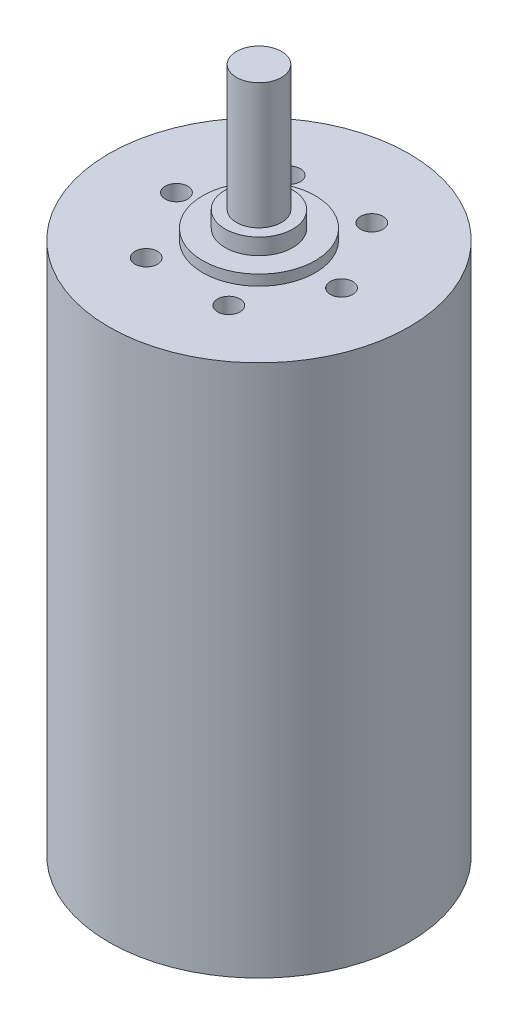
SolidWorks part; units mm, degrees
ref_plane "Front Plane" through (0, 0, 0) normal (0, 0, 1) x (1, 0, 0)
ref_plane "Top Plane" through (0, 0, 0) normal (0, 1, 0) x (1, 0, 0)
ref_plane "Right Plane" through (0, 0, 0) normal (1, 0, 0) x (0, 0, -1)
sketch "Sketch1" plane through (0, 0, 0) normal (0, 1, 0) x (1, 0, 0)
  circle A0 centre (0, 0) radius 20
  dimension "D1" = 40
extrude "Boss-Extrude1" add sketch "Sketch1" along normal blind 71
sketch "Sketch2" plane through (0, 71, 0) normal (0, 1, 0) x (1, 0, 0)
  circle A0 centre (0, 0) radius 7.5
  dimension "D1" = 15
extrude "Boss-Extrude2" add sketch "Sketch2" along normal blind 1.4
sketch "Sketch3" plane through (0, 72.4, 0) normal (0, 1, 0) x (1, 0, 0)
  circle A0 centre (0, 0) radius 4.5
  dimension "D1" = 9
extrude "Boss-Extrude3" add sketch "Sketch3" along normal blind 2.15
sketch "Sketch4" plane through (0, 74.55, 0) normal (0, 1, 0) x (1, 0, 0)
  circle A0 centre (0, 0) radius 3
  dimension "D1" = 6
extrude "Boss-Extrude4" add sketch "Sketch4" along normal blind 16.75
sketch "Sketch5" plane through (0, 71, 0) normal (0, 1, 0) x (1, 0, 0)
  circle A1 centre (-11, 0) radius 1.5
  dimension "D2" = 11
  dimension "D3" = 3
  dimension "D1" = 0
extrude "Cut-Extrude1" cut sketch "Sketch5" against normal blind 5
pattern_circular "CirPattern1" count 6 over 360 about axis through (0, 91.3, 0) along (0, -1, 0) of "Cut-Extrude1"
